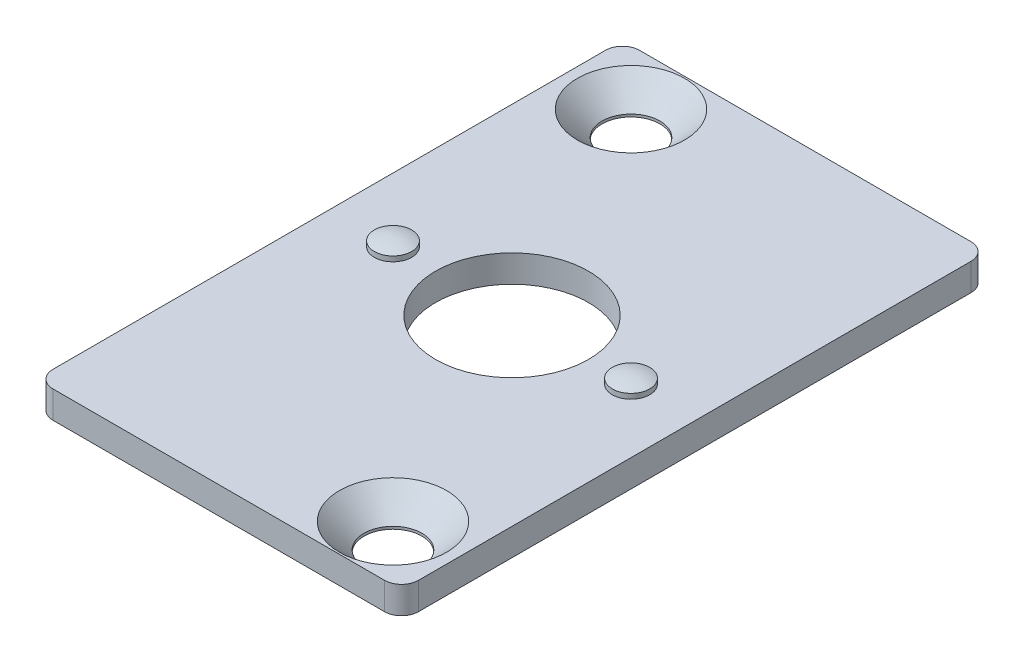
SolidWorks part; units mm, degrees
material "Chrome Stainless Steel"
ref_plane "Front Plane" through (0, 0, 0) normal (0, 0, 1) x (1, 0, 0)
ref_plane "Top Plane" through (0, 0, 0) normal (0, 1, 0) x (1, 0, 0)
ref_plane "Right Plane" through (0, 0, 0) normal (1, 0, 0) x (0, 0, -1)
sketch "BaseS" plane through (0, 0, 0) normal (0, 1, 0) x (1, 0, 0)
  line L1 (-10.75, 17.25) -> (10.75, 17.25)
  line L2 (-10.75, 17.25) -> (-10.75, -17.25)
  line L3 (-10.75, -17.25) -> (10.75, -17.25)
  line L4 (10.75, 17.25) -> (10.75, -17.25)
  line L5 (-10.75, 17.25) -> (10.75, -17.25) construction
  line L6 (-10.75, -17.25) -> (10.75, 17.25) construction
  point P0 (0, 0)
  dimension "Width" = 21.5
  dimension "Length" = 34.5
extrude "BASE" add sketch "BaseS" against normal blind 1.6
hole_wizard "CSK for M3 Flat Head Machine Screw1" positions "Sketch2" profile "Sketch3" countersink size "M3" standard "ANSI Metric"
sketch "Sketch2" plane through (0, 0, 0) normal (0, 1, 0) x (1, 0, 0)
  line L0 (-10.75, 17.25) -> (-10.75, -17.25) construction
  line L1 (10.75, -17.25) -> (10.75, 17.25) construction
  line L2 (10.75, 17.25) -> (-10.75, 17.25) construction
  line L3 (-10.75, -17.25) -> (10.75, -17.25) construction
  point P0 (-7, 14)
  point P2 (7, -14)
  dimension "XLoc1" = 3.75
  dimension "XLoc2" = 3.75
  dimension "YLoc1" = 3.25
  dimension "YLoc2" = 3.25
  dimension "YH2HRefDim" = 28
  dimension "XH2HRefDim" = 14
sketch "Sketch3" plane through (-7, 0, -14) normal (1, 0, 0) x (0, 0, 1)
  line L0 (0, 0) -> (0, 12.0215)
  line L1 (0, 12.0215) -> (1.7, 11)
  line L2 (1.7, 11) -> (1.7, 1.45)
  line L3 (1.7, 1.45) -> (3.15, 0)
  line L5 (3.15, 0) -> (0, 0)
  line L6 (-1.7, 1.45) -> (-3.15, 0) construction
  line L10 (0, 12.0215) -> (-1.7, 11) construction
  line L11 (0, -6.35) -> (0, 107.95) construction
  dimension "Hole Dia." = 3.4
  dimension "Hole Depth" = 11
  dimension "Near C'Sink Dia." = 6.3
  dimension "Near C'Sink Angle" = 90
  dimension "Drill Angle" = 118
sketch "BoreS" plane through (0, 0, 0) normal (0, 1, 0) x (1, 0, 0)
  circle A0 centre (0, 0) radius 4.5
  dimension "Dia" = 9
extrude "BORE" cut sketch "BoreS" against normal through all
sketch "LockingFeatureS" plane through (0, 0, 0) normal (0, 1, 0) x (1, 0, 0)
  line L0 (0, 0) -> (-7, 0) construction
  circle A0 centre (-7, 0) radius 1.1
  circle A1 centre (0, 0) radius 4.5 construction
  dimension "Dia" = 2.2
  dimension "XLoc" = 7
extrude "LOCKING FEATURE" add sketch "LockingFeatureS" along normal blind 0.3
dome "LF DOME" faces to dome 1 distance 0.2 reverse direction no elliptical dome no face at (-7, 0.3, 1.1) parameters "Height"=0.2
mirror "LF HM" about plane through (0, 0, 0) normal (1, 0, 0) of "LF DOME", "LOCKING FEATURE"
sketch "LFBottomCut" plane through (0, -1.6, 0) normal (0, -1, 0) x (-1, 0, 0)
  circle A0 centre (7, 0) radius 1.1
  circle A1 centre (-7, 0) radius 1.1
  circle A2 centre (7, 0) radius 1.1 construction
extrude "LF BOTTOM CUT" cut sketch "LFBottomCut" against normal blind 0.3
fillet "BASE FILLET" radius 1 4 edges at (-10.75, -0.8, -17.25) (10.75, -0.8, -17.25) (10.75, -0.8, 17.25) (-10.75, -0.8, 17.25)
